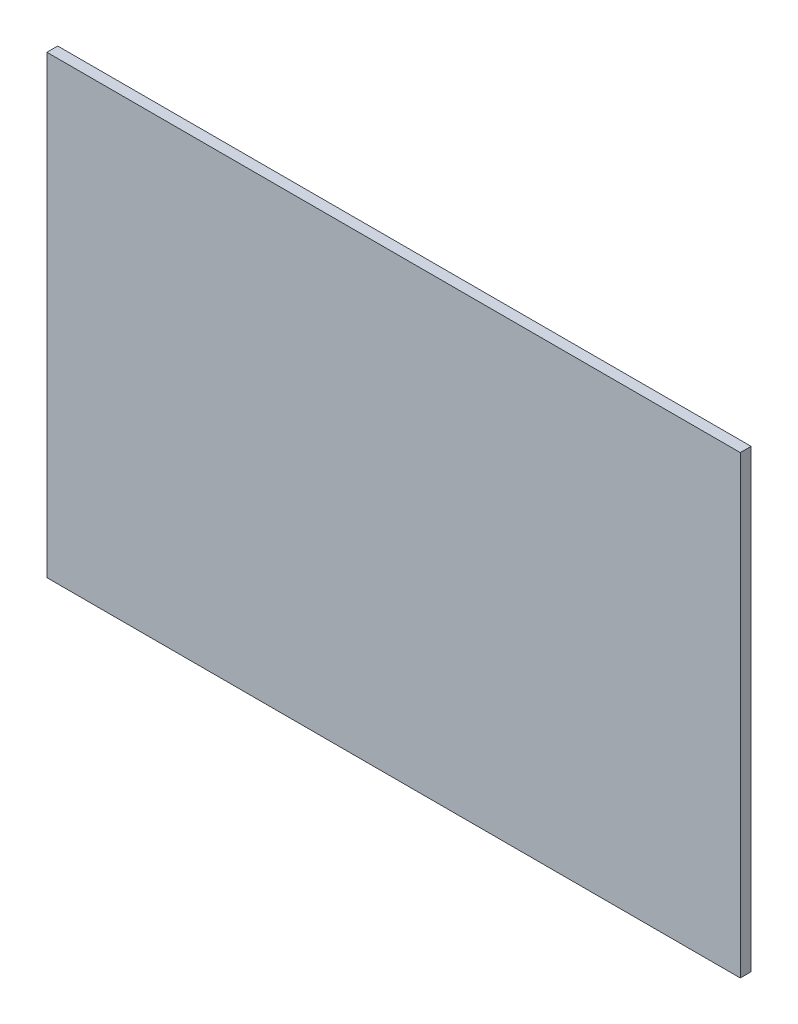
SolidWorks part; units mm, degrees
material "Oak"
ref_plane "Front Plane" through (0, 0, 0) normal (0, 0, 1) x (1, 0, 0)
ref_plane "Top Plane" through (0, 0, 0) normal (0, 1, 0) x (1, 0, 0)
ref_plane "Right Plane" through (0, 0, 0) normal (1, 0, 0) x (0, 0, -1)
sketch "Sketch1" plane through (0, 0, 0) normal (0, 0, 1) x (1, 0, 0)
  line L1 (-160, 105) -> (160, 105)
  line L2 (-160, 105) -> (-160, -105)
  line L3 (-160, -105) -> (160, -105)
  line L4 (160, 105) -> (160, -105)
  line L5 (-160, 105) -> (160, -105) construction
  line L6 (-160, -105) -> (160, 105) construction
  point P0 (0, 0)
  dimension "D1" = 320
  dimension "D2" = 210
base flange "Base-Flange1" sketch "Sketch1" thickness 5 reverse thickness direction no parameters "D1"=0.7366
sketch "Bend-Lines1" [suppressed] plane through (0, 0, 0) normal (0, 1, 0) x (1, 0, 0)
sketch "Bounding-Box1" [suppressed] plane through (0, 0, 0) normal (0, 1, 0) x (1, 0, 0)
sheet metal parameters "Sheet-Metal1" thickness 5 parameters "D1"=0.7366
flat pattern "Flat-Pattern1" [suppressed]
sketch "Bend-Lines2" plane through (0, 0, 0) normal (0, 1, 0) x (1, 0, 0)
sketch3d "Bounding-Box2" [suppressed]
  line L0 (160, -105, 0) -> (-160, -105, 0) construction
  line L1 (160, 105, 0) -> (-160, 105, 0) construction
  line L2 (160, -105, 0) -> (160, 105, 0) construction
  line L3 (-160, -105, 0) -> (-160, 105, 0) construction
